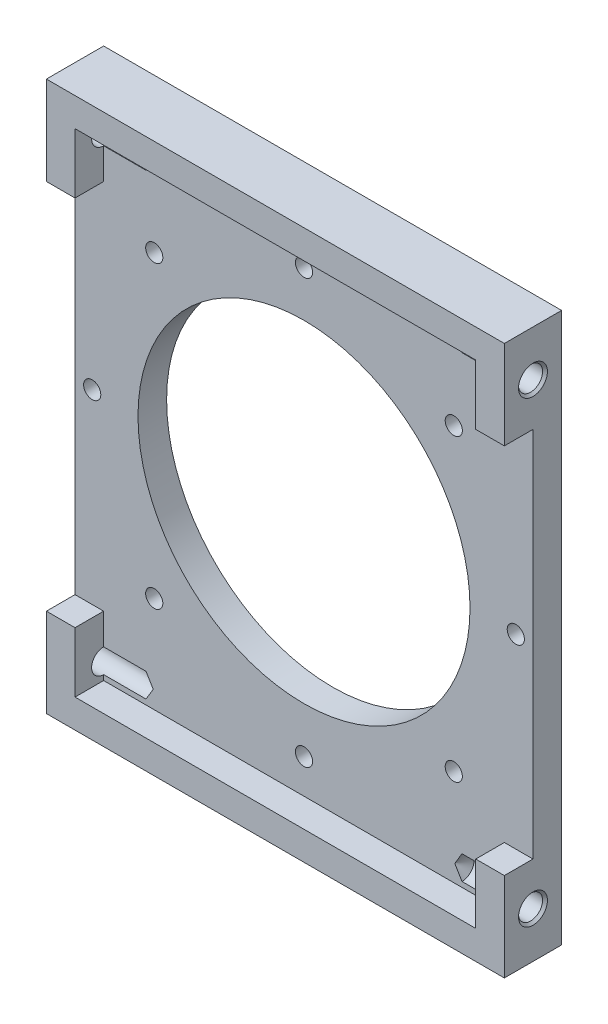
SolidWorks part; units mm, degrees
ref_plane "Front Plane" through (0, 0, 0) normal (0, 0, 1) x (1, 0, 0)
ref_plane "Top Plane" through (0, 0, 0) normal (0, 1, 0) x (1, 0, 0)
ref_plane "Right Plane" through (0, 0, 0) normal (1, 0, 0) x (0, 0, -1)
sketch "Sketch1" plane through (0, 0, 0) normal (0, 0, 1) x (1, 0, 0)
  line L1 (-40, 48) -> (40, 48)
  line L2 (-40, 48) -> (-40, -48)
  line L3 (-40, -48) -> (40, -48)
  line L4 (40, 48) -> (40, -48)
  line L5 (-40, 48) -> (40, -48) construction
  line L6 (-40, -48) -> (40, 48) construction
  line L7 (-35, 43) -> (35, 43)
  line L8 (-35, 43) -> (-35, -43)
  line L9 (-35, -43) -> (35, -43)
  line L10 (35, 43) -> (35, -43)
  line L11 (-35, 43) -> (35, -43) construction
  line L12 (-35, -43) -> (35, 43) construction
  circle A0 centre (0, 0) radius 29
  point P0 (0, 0)
  point P6 (0, 0)
  dimension "D5" = 58
  dimension "D1" = 96
  dimension "D2" = 80
  dimension "D3" = 70
  dimension "D4" = 86
extrude "Boss-Extrude1" add sketch "Sketch1" along normal blind 5 contours L10 L7 L8 L9 region at (0, 41.8911, 0)
extrude "Boss-Extrude2" add sketch "Sketch1<3>" along normal blind 10 contours L4 L1 L2 L3 L7 L10 L9 L8 region at (0, 46.7504, 0)
sketch "Sketch1<3>" plane through (0, 0, 0) normal (0, 0, 1) x (1, 0, 0) same geometry as "Sketch1"
ref_plane "Plane1" through (40, 0, 0) normal (1, 0, 0) x (0, 0, -1)
hole_wizard "M5 Tapped Hole1" positions "Sketch2" profile "Sketch3" tap size "M5" standard "ISO"
sketch "Sketch2" plane through (40, 0, 0) normal (1, 0, 0) x (0, 0, -1)
  line L0 (0, 0) -> (-24.6641, 0) construction
  line L1 (-5, 0) -> (-5, 43.859) construction
  line L2 (-5, 43.859) -> (-5, -49.7014) construction
  point P0 (-5, 40)
  point P2 (-5, -40)
  point P21 (0, 0)
  point P22 (-4.2408, 34.7283)
  point P23 (-4.2408, -37.9681)
  point P24 (0, 0)
  dimension "D1" = 40
  dimension "D2" = 40
  dimension "D3" = 5
sketch "Sketch3" plane through (40, 40, 5) normal (0, 1, 0) x (0, 0, -1)
  line L0 (0, 0) -> (0, 13.6618)
  line L1 (0, 13.6618) -> (2.1, 12.4)
  line L2 (2.1, 12.4) -> (2.1, 0.425)
  line L3 (2.1, 0.425) -> (2.525, 0)
  line L5 (2.525, 0) -> (0, 0)
  line L6 (-2.1, 0.425) -> (-2.525, 0) construction
  line L10 (0, 13.6618) -> (-2.1, 12.4) construction
  line L11 (0, -6.35) -> (0, 107.95) construction
  dimension "Tap Drill Dia." = 4.2
  dimension "Tap Drill Depth" = 12.4
  dimension "Near C'Sink Dia." = 5.05
  dimension "Near C'Sink Angle" = 90
  dimension "Drill Angle" = 118
cosmetic thread "Hole Thread1" parameters "D1"=10, "D2"=5
cosmetic thread "Hole Thread2" parameters "D1"=10, "D2"=5
hole_wizard "M5 Tapped Hole2" positions "Sketch4" profile "Sketch5" tap size "M5" standard "ISO"
sketch "Sketch4" plane through (-40, 0, 0) normal (-1, 0, 0) x (0, 0, 1)
  line L0 (0, 0) -> (28.8511, 0) construction
  line L3 (5, 0) -> (5, -61.3848) construction
  line L4 (5, -61.3848) -> (5, 53.7585) construction
  point P13 (5, 40)
  point P15 (5, -40)
  dimension "D1" = 40
  dimension "D2" = 40
sketch "Sketch5" plane through (-40, -40, 5) normal (0, 1, 0) x (0, 0, 1)
  line L0 (0, 0) -> (0, 13.6618)
  line L1 (0, 13.6618) -> (2.1, 12.4)
  line L2 (2.1, 12.4) -> (2.1, 0.425)
  line L3 (2.1, 0.425) -> (2.525, 0)
  line L5 (2.525, 0) -> (0, 0)
  line L6 (-2.1, 0.425) -> (-2.525, 0) construction
  line L10 (0, 13.6618) -> (-2.1, 12.4) construction
  line L11 (0, -6.35) -> (0, 107.95) construction
  dimension "Tap Drill Dia." = 4.2
  dimension "Tap Drill Depth" = 12.4
  dimension "Near C'Sink Dia." = 5.05
  dimension "Near C'Sink Angle" = 90
  dimension "Drill Angle" = 118
cosmetic thread "Hole Thread3" parameters "D1"=10, "D2"=5
cosmetic thread "Hole Thread4" parameters "D1"=10, "D2"=5
ref_plane "Plane2" through (0, 0, 10) normal (0, 0, 1) x (1, 0, 0)
sketch "Sketch7" plane through (0, 0, 10) normal (0, 0, 1) x (1, 0, 0)
  line L1 (-40, 32.5) -> (40, 32.5)
  line L2 (-40, 32.5) -> (-40, -32.5)
  line L3 (-40, -32.5) -> (40, -32.5)
  line L4 (40, 32.5) -> (40, -32.5)
  line L5 (-40, 32.5) -> (40, -32.5) construction
  line L6 (-40, -32.5) -> (40, 32.5) construction
  point P0 (0, 0)
  dimension "D1" = 80
  dimension "D2" = 65
extrude "Cut-Extrude1" cut sketch "Sketch7" against normal blind 5
sketch "Sketch6" plane through (0, 0, 0) normal (0, 0, 1) x (1, 0, 0)
  line L0 (0, 0) -> (0, 52.2631) construction
  circle A0 centre (0, 37) radius 1.5
  circle A1 centre (26.163, 26.163) radius 1.5
  circle A2 centre (37, 0) radius 1.5
  circle A3 centre (26.163, -26.163) radius 1.5
  circle A4 centre (0, -37) radius 1.5
  circle A5 centre (-26.163, -26.163) radius 1.5
  circle A6 centre (-37, 0) radius 1.5
  circle A7 centre (-26.163, 26.163) radius 1.5
  point P3 (0, 37)
  point P22 (0, 0)
  dimension "D2" = 3
  dimension "D1" = 37
  dimension "D3" = 8
extrude "Cut-Extrude2" cut sketch "Sketch6" along normal blind 5
